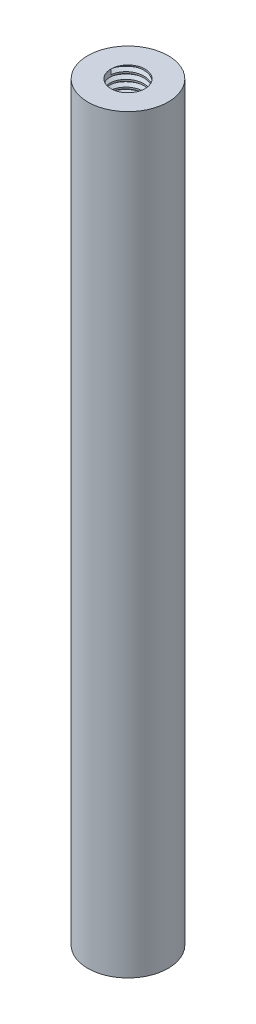
SolidWorks part; units mm, degrees
material "6061-T6 (SS)"
ref_plane "Front Plane" through (0, 0, 0) normal (0, 0, 1) x (1, 0, 0)
ref_plane "Top Plane" through (0, 0, 0) normal (0, 1, 0) x (1, 0, 0)
ref_plane "Right Plane" through (0, 0, 0) normal (1, 0, 0) x (0, 0, -1)
other "Bounding Box"
ref_plane "Default Plane" through (13.8565, 3.175, 6.7999) normal (0, -1, 0) x (-1, 0, 0)
sketch "Sketch1" plane through (0, 0, 0) normal (0, 1, 0) x (1, 0, 0)
  circle A0 centre (0, 0) radius 4.7625
  circle A1 centre (0, 0) radius 2.0193
  dimension "D1" = 9.525
  dimension "D2" = 4.0386
extrude "Boss-Extrude1" add sketch "Sketch1" along normal mid plane 88.9
thread "Thread1" pitch 0.7937 method cut profile "Thread Profile2" start angle 0, offset 0, length 9.525, pitch 0.7937, diameter 4.0386
ref_plane "Plane2" through (-2.0193, 44.45, 0) normal (0, 0, 1) x (-1, 0, 0)
sketch "Thread Profile2" plane through (-2.0193, 44.45, 0) normal (0, 0, 1) x (-1, 0, 0)
  line L0 (0, 0) -> (0, 0.7937) construction
  line L1 (0, 0) -> (0.4296, 0.248)
  line L2 (0.4296, 0.248) -> (0.4296, 0.3473)
  line L3 (0.4296, 0.3473) -> (0, 0.5953)
  line L4 (0.4296, 0.2977) -> (0, 0.2977) construction
  line L11 (0, 0) -> (0, 0.5953)
  point P2 (0, 0)
  dimension "Pitch" = 0.7937
  dimension "Profile_Angle" = 60
  dimension "Profile_Land" = 0.0992
  dimension "Profile_Height" = 0.4296
mirror "Mirror3" about plane through (0, 0, 0) normal (0, 1, 0) of "Thread1"
